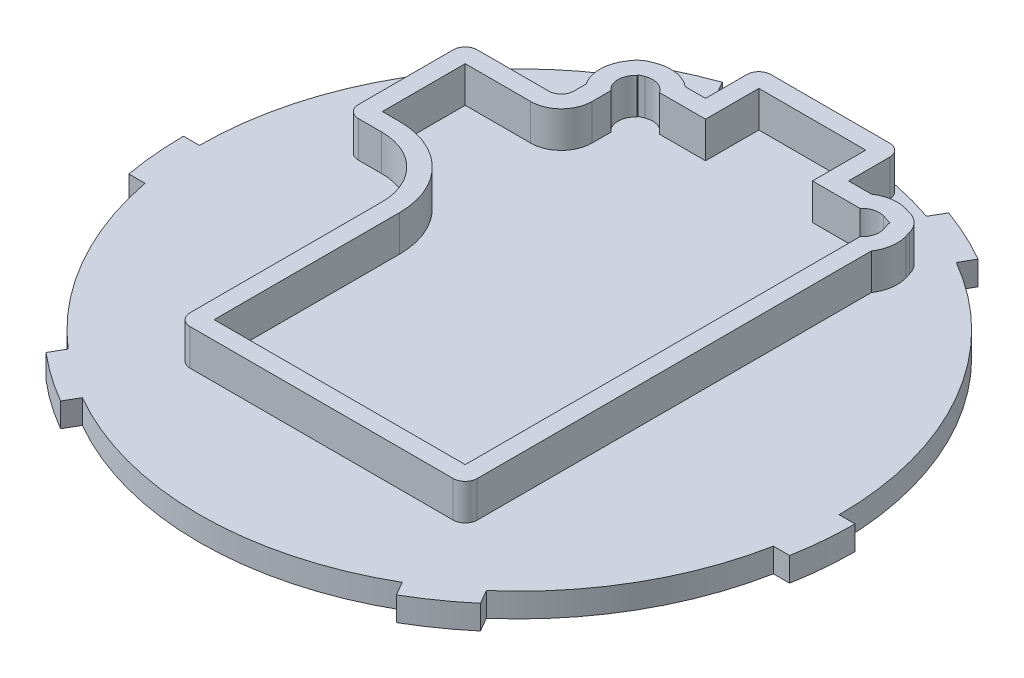
SolidWorks part; units mm, degrees
ref_plane "Front Plane" through (0, 0, 0) normal (0, 0, 1) x (1, 0, 0)
ref_plane "Top Plane" through (0, 0, 0) normal (0, 1, 0) x (1, 0, 0)
ref_plane "Right Plane" through (0, 0, 0) normal (1, 0, 0) x (0, 0, -1)
sketch "Sketch1" plane through (0, 0, 0) normal (0, 1, 0) x (1, 0, 0)
  line L0 (13.3111, 23.0555) -> (13.9742, 24.204) construction
  line L1 (-13.9742, -24.204) -> (-13.3111, -23.0555) construction
  line L2 (-17.4043, -20.1452) -> (-18.0789, -21.3135) construction
  line L3 (13.9742, -24.204) -> (13.3111, -23.0555) construction
  line L4 (17.4043, -20.1452) -> (18.0789, -21.3135) construction
  line L5 (27.4975, -5) -> (26.1484, -5) construction
  line L6 (27.9484, 0) -> (26.6221, 0) construction
  line L7 (9.4186, 26.3135) -> (8.7441, 25.1452) construction
  line L8 (6, 25.9372) -> (6, 21.5) construction
  line L9 (6, 21.5) -> (7.8417, 21.5) construction
  line L10 (12, 17.3417) -> (12, -16.5) construction
  line L11 (12, 17.3417) -> (12, -16.5)
  line L12 (6, 21.5) -> (7.8417, 21.5)
  line L13 (6, 25.9372) -> (6, 21.5)
  line L14 (9.4186, 26.3135) -> (8.7441, 25.1452)
  line L15 (13.3111, 23.0555) -> (13.9742, 24.204)
  line L16 (27.9484, 0) -> (26.6221, 0)
  line L17 (27.4975, -5) -> (26.1484, -5)
  line L18 (17.4043, -20.1452) -> (18.0789, -21.3135)
  line L19 (13.9742, -24.204) -> (13.3111, -23.0555)
  line L20 (-17.4043, -20.1452) -> (-18.0789, -21.3135)
  line L21 (-13.9742, -24.204) -> (-13.3111, -23.0555)
  line L22 (12, -16.5) -> (-12, -16.5) construction
  line L23 (12, -16.5) -> (-12, -16.5)
  line L24 (0, 0) -> (0, -16.5) construction
  line L25 (-13.3111, 23.0555) -> (-13.9742, 24.204) construction
  line L26 (-9.4186, 26.3135) -> (-8.7441, 25.1452) construction
  line L27 (-6, 25.9372) -> (-6, 21.5) construction
  line L28 (-7.6227, 21.5) -> (-6, 21.5) construction
  line L29 (-12, 20.8183) -> (-12, 21.5) construction
  line L30 (-12, 16.5) -> (-12, 17.5017) construction
  line L31 (-20, 15.5) -> (-13, 15.5) construction
  line L32 (-12, -16.5) -> (-12, 0.5) construction
  line L33 (-17, 5.5) -> (-20, 5.5) construction
  line L34 (-20, 5.5) -> (-20, 15.5) construction
  line L35 (-13.3111, 23.0555) -> (-13.9742, 24.204)
  line L36 (-9.4186, 26.3135) -> (-8.7441, 25.1452)
  line L37 (-6, 25.9372) -> (-6, 21.5)
  line L38 (-7.6227, 21.5) -> (-6, 21.5)
  line L39 (-12, 20.8183) -> (-12, 21.5)
  line L40 (-12, 16.5) -> (-12, 17.5017)
  line L41 (-20, 15.5) -> (-13, 15.5)
  line L42 (-12, -16.5) -> (-12, 0.5)
  line L43 (-17, 5.5) -> (-20, 5.5)
  line L44 (-20, 5.5) -> (-20, 15.5)
  line L45 (-26.1484, -5) -> (-27.4975, -5) construction
  line L46 (-26.6221, 0) -> (-27.9484, 0) construction
  line L47 (-26.6221, 0) -> (-27.9484, 0)
  line L48 (-26.1484, -5) -> (-27.4975, -5)
  arc A1 (-13.3111, -23.0555) -> (13.3111, -23.0555) centre (0, 0) ccw construction
  arc A2 (-18.0789, -21.3135) -> (-13.9742, -24.204) centre (0, 0) ccw construction
  arc A3 (-26.1484, -5) -> (-17.4043, -20.1452) centre (0, 0) ccw construction
  arc A4 (13.9742, -24.204) -> (18.0789, -21.3135) centre (0, 0) ccw construction
  arc A5 (17.4043, -20.1452) -> (26.1484, -5) centre (0, 0) ccw construction
  arc A6 (27.4975, -5) -> (27.9484, 0) centre (0, 0) ccw construction
  arc A7 (26.6221, 0) -> (13.3111, 23.0555) centre (0, 0) ccw construction
  arc A8 (13.9742, 24.204) -> (9.4186, 26.3135) centre (0, 0) ccw construction
  arc A9 (8.7441, 25.1452) -> (6, 25.9372) centre (0, 0) ccw construction
  arc A10 (12, 17.3417) -> (12.3619, 19.8996) centre (9.5, 19) ccw construction
  arc A11 (10.3996, 21.8619) -> (7.8417, 21.5) centre (9.5, 19) ccw construction
  arc A12 (10.3996, 21.8619) -> (12, 21.5) centre (13.3982, 31.4018) ccw construction
  arc A13 (12, 21.5) -> (12.3619, 19.8996) centre (21.9018, 22.8982) ccw construction
  arc A14 (12, 17.3417) -> (12.3619, 19.8996) centre (9.5, 19) ccw
  arc A15 (12, 21.5) -> (12.3619, 19.8996) centre (21.9018, 22.8982) ccw
  arc A16 (10.3996, 21.8619) -> (12, 21.5) centre (13.3982, 31.4018) ccw
  arc A17 (10.3996, 21.8619) -> (7.8417, 21.5) centre (9.5, 19) ccw
  arc A18 (8.7441, 25.1452) -> (6, 25.9372) centre (0, 0) ccw
  arc A19 (13.9742, 24.204) -> (9.4186, 26.3135) centre (0, 0) ccw
  arc A20 (26.6221, 0) -> (13.3111, 23.0555) centre (0, 0) ccw
  arc A21 (27.4975, -5) -> (27.9484, 0) centre (0, 0) ccw
  arc A22 (17.4043, -20.1452) -> (26.1484, -5) centre (0, 0) ccw
  arc A23 (13.9742, -24.204) -> (18.0789, -21.3135) centre (0, 0) ccw
  arc A24 (-26.1484, -5) -> (-17.4043, -20.1452) centre (0, 0) ccw
  arc A25 (-18.0789, -21.3135) -> (-13.9742, -24.204) centre (0, 0) ccw
  arc A26 (-13.3111, -23.0555) -> (13.3111, -23.0555) centre (0, 0) ccw
  arc A27 (-13.3111, 23.0555) -> (-26.6221, 0) centre (0, 0) ccw construction
  arc A28 (-9.4186, 26.3135) -> (-13.9742, 24.204) centre (0, 0) ccw construction
  arc A29 (-6, 25.9372) -> (-8.7441, 25.1452) centre (0, 0) ccw construction
  arc A30 (-7.6227, 21.5) -> (-10.6213, 21.9425) centre (-9.5, 19.16) ccw construction
  arc A31 (-12, 21.5) -> (-10.6213, 21.9425) centre (-14.3589, 31.2178) ccw construction
  arc A32 (-12, 20.8183) -> (-12, 17.5017) centre (-9.5, 19.16) ccw construction
  arc A33 (-13, 15.5) -> (-12, 16.5) centre (-13, 16.5) ccw construction
  arc A34 (-12, 0.5) -> (-17, 5.5) centre (-17, 0.5) ccw construction
  arc A35 (-13.3111, 23.0555) -> (-26.6221, 0) centre (0, 0) ccw
  arc A36 (-9.4186, 26.3135) -> (-13.9742, 24.204) centre (0, 0) ccw
  arc A37 (-6, 25.9372) -> (-8.7441, 25.1452) centre (0, 0) ccw
  arc A38 (-7.6227, 21.5) -> (-10.6213, 21.9425) centre (-9.5, 19.16) ccw
  arc A39 (-12, 21.5) -> (-10.6213, 21.9425) centre (-14.3589, 31.2178) ccw
  arc A40 (-12, 20.8183) -> (-12, 17.5017) centre (-9.5, 19.16) ccw
  arc A41 (-13, 15.5) -> (-12, 16.5) centre (-13, 16.5) ccw
  arc A42 (-12, 0.5) -> (-17, 5.5) centre (-17, 0.5) ccw
  arc A43 (-27.9484, 0) -> (-27.4975, -5) centre (0, 0) ccw construction
  arc A44 (-27.9484, 0) -> (-27.4975, -5) centre (0, 0) ccw
  circle A45 centre (0, 0) radius 26.6221
extrude "Boss-Extrude1" add sketch "Sketch1" along normal blind 2 contours L13 A45 L37 L38 A38 A39 L39 A40 L40 A41 L41 L44 L43 A42 L42 L23 L11 A14 A15 A16 A17 L12 | A26 A45 A22 A20 A18 L13 L12 A17 A16 A15 A14 L11 L23 L42 A42 L43 L44 L41 A41 L40 A40 L39 A39 A38 L38 L37 A37 A35 A24 | A45 L15 A19 L14 | A45 L36 A36 L35 | A45 L17 A21 L16 | A45 L19 A23 L18 | A45 L20 A25 L21 | A45 L47 A44 L48 region at (13.2112, 0, -18.4749) region at (-1.2783, 0, -4.3933) region at (11.3943, 0, -24.7497) region at (-11.3943, 0, -24.7497) region at (27.131, 0, 2.5071) region at (-27.131, 0, 2.5071) region at (15.7367, 0, 22.2426) region at (-15.7367, 0, 22.2426)
sketch "Sketch2" plane through (0, 0, 0) normal (0, -1, 0) x (1, 0, 0)
  line L0 (-6, -25.9372) -> (6, -25.9372) construction
  line L1 (-5.95, -25.8872) -> (5.95, -25.8872)
  line L2 (5.95, -21.45) -> (5.95, -25.8872)
  line L3 (7.8568, -21.45) -> (5.95, -21.45)
  line L4 (11.95, 16.45) -> (11.95, -17.3568)
  line L5 (-11.95, 16.45) -> (11.95, 16.45)
  line L6 (-11.95, -0.5) -> (-11.95, 16.45)
  line L7 (-19.95, -5.55) -> (-17, -5.55)
  line L8 (-19.95, -15.45) -> (-19.95, -5.55)
  line L9 (-13, -15.45) -> (-19.95, -15.45)
  line L10 (-11.95, -17.5168) -> (-11.95, -16.5)
  line L11 (-11.95, -21.4608) -> (-11.95, -20.8031)
  line L12 (-5.95, -21.45) -> (-7.6404, -21.45)
  line L13 (-5.95, -25.8872) -> (-5.95, -21.45)
  line L24 (-12, -0.5) -> (-12, 16.5)
  line L25 (-12, 16.5) -> (12, 16.5)
  line L26 (12, 16.5) -> (12, -17.3417)
  line L27 (7.8417, -21.5) -> (6, -21.5)
  line L28 (6, -21.5) -> (6, -25.9372)
  line L29 (8.7441, -25.1452) -> (9.4186, -26.3135)
  line L30 (13.9742, -24.204) -> (13.3111, -23.0555)
  line L31 (26.6221, 0) -> (27.9484, 0)
  line L32 (27.4975, 5) -> (26.1484, 5)
  line L33 (17.4043, 20.1452) -> (18.0789, 21.3135)
  line L34 (13.9742, 24.204) -> (13.3111, 23.0555)
  line L35 (-13.3111, 23.0555) -> (-13.9742, 24.204)
  line L36 (-18.0789, 21.3135) -> (-17.4043, 20.1452)
  line L37 (-26.1484, 5) -> (-27.4975, 5)
  line L38 (-27.9484, 0) -> (-26.6221, 0)
  line L39 (-13.3111, -23.0555) -> (-13.9742, -24.204)
  line L40 (-9.4186, -26.3135) -> (-8.7441, -25.1452)
  line L41 (-6, -25.9372) -> (-6, -21.5)
  line L42 (-6, -21.5) -> (-7.6227, -21.5)
  line L43 (-12, -21.5) -> (-12, -20.8183)
  line L44 (-12, -17.5017) -> (-12, -16.5)
  line L45 (-13, -15.5) -> (-20, -15.5)
  line L46 (-20, -15.5) -> (-20, -5.5)
  line L47 (-20, -5.5) -> (-17, -5.5)
  line L48 (-12, -0.5) -> (-12, 16.5) construction
  line L49 (-12, 16.5) -> (12, 16.5) construction
  line L50 (12, 16.5) -> (12, -17.3417) construction
  line L51 (7.8417, -21.5) -> (6, -21.5) construction
  line L52 (6, -21.5) -> (6, -25.9372) construction
  line L65 (-6, -25.9372) -> (-6, -21.5) construction
  line L66 (-6, -21.5) -> (-7.6227, -21.5) construction
  line L67 (-12, -21.5) -> (-12, -20.8183) construction
  line L68 (-12, -17.5017) -> (-12, -16.5) construction
  line L69 (-13, -15.5) -> (-20, -15.5) construction
  line L70 (-20, -15.5) -> (-20, -5.5) construction
  line L71 (-20, -5.5) -> (-17, -5.5) construction
  arc A0 (7.8568, -21.45) -> (10.3846, -21.8142) centre (9.5, -19) ccw
  arc A1 (11.9558, -21.4558) -> (10.3846, -21.8142) centre (13.3982, -31.4018) ccw
  arc A3 (12.3142, -19.8846) -> (11.9558, -21.4558) centre (21.9018, -22.8982) ccw
  arc A4 (12.3142, -19.8846) -> (11.95, -17.3568) centre (9.5, -19) ccw
  arc A5 (-17, -5.55) -> (-11.95, -0.5) centre (-17, -0.5) ccw
  arc A6 (-11.95, -16.5) -> (-13, -15.45) centre (-13, -16.5) ccw
  arc A7 (-11.95, -17.5168) -> (-11.95, -20.8031) centre (-9.5, -19.16) ccw
  arc A8 (-10.6026, -21.8962) -> (-11.95, -21.4608) centre (-14.3589, -31.2178) ccw
  arc A9 (-10.6026, -21.8962) -> (-7.6404, -21.45) centre (-9.5, -19.16) ccw
  arc A24 (12.3619, -19.8996) -> (12, -17.3417) centre (9.5, -19) ccw
  arc A25 (12.3619, -19.8996) -> (12, -21.5) centre (21.9018, -22.8982) ccw
  arc A26 (12, -21.5) -> (10.3996, -21.8619) centre (13.3982, -31.4018) ccw
  arc A27 (7.8417, -21.5) -> (10.3996, -21.8619) centre (9.5, -19) ccw
  arc A28 (6, -25.9372) -> (8.7441, -25.1452) centre (0, 0) ccw
  arc A29 (9.4186, -26.3135) -> (13.9742, -24.204) centre (0, 0) ccw
  arc A30 (13.3111, -23.0555) -> (26.6221, 0) centre (0, 0) ccw
  arc A31 (27.9484, 0) -> (27.4975, 5) centre (0, 0) ccw
  arc A32 (26.1484, 5) -> (17.4043, 20.1452) centre (0, 0) ccw
  arc A33 (18.0789, 21.3135) -> (13.9742, 24.204) centre (0, 0) ccw
  arc A34 (13.3111, 23.0555) -> (-13.3111, 23.0555) centre (0, 0) ccw
  arc A35 (-13.9742, 24.204) -> (-18.0789, 21.3135) centre (0, 0) ccw
  arc A36 (-17.4043, 20.1452) -> (-26.1484, 5) centre (0, 0) ccw
  arc A37 (-27.4975, 5) -> (-27.9484, 0) centre (0, 0) ccw
  arc A38 (-26.6221, 0) -> (-13.3111, -23.0555) centre (0, 0) ccw
  arc A39 (-13.9742, -24.204) -> (-9.4186, -26.3135) centre (0, 0) ccw
  arc A40 (-8.7441, -25.1452) -> (-6, -25.9372) centre (0, 0) ccw
  arc A41 (-10.6213, -21.9425) -> (-7.6227, -21.5) centre (-9.5, -19.16) ccw
  arc A42 (-10.6213, -21.9425) -> (-12, -21.5) centre (-14.3589, -31.2178) ccw
  arc A43 (-12, -17.5017) -> (-12, -20.8183) centre (-9.5, -19.16) ccw
  arc A44 (-12, -16.5) -> (-13, -15.5) centre (-13, -16.5) ccw
  arc A45 (-17, -5.5) -> (-12, -0.5) centre (-17, -0.5) ccw
  arc A46 (12.3619, -19.8996) -> (12, -17.3417) centre (9.5, -19) ccw construction
  arc A47 (12.3619, -19.8996) -> (12, -21.5) centre (21.9018, -22.8982) ccw construction
  arc A48 (12, -21.5) -> (10.3996, -21.8619) centre (13.3982, -31.4018) ccw construction
  arc A49 (7.8417, -21.5) -> (10.3996, -21.8619) centre (9.5, -19) ccw construction
  arc A63 (-10.6213, -21.9425) -> (-7.6227, -21.5) centre (-9.5, -19.16) ccw construction
  arc A64 (-10.6213, -21.9425) -> (-12, -21.5) centre (-14.3589, -31.2178) ccw construction
  arc A65 (-12, -17.5017) -> (-12, -20.8183) centre (-9.5, -19.16) ccw construction
  arc A66 (-12, -16.5) -> (-13, -15.5) centre (-13, -16.5) ccw construction
  arc A67 (-17, -5.5) -> (-12, -0.5) centre (-17, -0.5) ccw construction
  dimension "D1" = 0.05
  dimension "D2" = 0
extrude "Boss-Extrude2" add sketch "Sketch2" against normal blind 5
sketch "Sketch4" plane through (0, 5, 0) normal (0, 1, 0) x (-1, 0, 0)
  line L26 (4.45, -24.3872) -> (4.45, -19.95)
  line L27 (-4.45, -24.3872) -> (4.45, -24.3872)
  line L28 (-4.45, -19.95) -> (-4.45, -24.3872)
  line L29 (-8.4046, -19.95) -> (-4.45, -19.95)
  line L30 (-10.45, 14.95) -> (-10.45, -17.9046)
  line L31 (10.45, 14.95) -> (-10.45, 14.95)
  line L32 (10.45, -0.5) -> (10.45, 14.95)
  line L33 (18.45, -7.05) -> (17, -7.05)
  line L34 (18.45, -13.95) -> (18.45, -7.05)
  line L35 (13, -13.95) -> (18.45, -13.95)
  line L36 (10.45, -18.0645) -> (10.45, -16.5)
  line L37 (10.45, -20.3494) -> (10.45, -20.2554)
  line L38 (4.45, -19.95) -> (8.2841, -19.95)
  line L39 (4.45, -24.3872) -> (4.45, -19.95)
  line L40 (-4.45, -24.3872) -> (4.45, -24.3872)
  line L41 (-4.45, -19.95) -> (-4.45, -24.3872)
  line L42 (-8.4046, -19.95) -> (-4.45, -19.95)
  line L43 (-10.45, 14.95) -> (-10.45, -17.9046)
  line L44 (10.45, 14.95) -> (-10.45, 14.95)
  line L45 (10.45, -0.5) -> (10.45, 14.95)
  line L46 (18.45, -7.05) -> (17, -7.05)
  line L47 (18.45, -13.95) -> (18.45, -7.05)
  line L48 (13, -13.95) -> (18.45, -13.95)
  line L49 (10.45, -18.0645) -> (10.45, -16.5)
  line L50 (10.45, -20.3494) -> (10.45, -20.2554)
  line L51 (4.45, -19.95) -> (8.2841, -19.95)
  arc A18 (-9.9348, -20.3833) -> (-8.4046, -19.95) centre (-9.5, -19) ccw
  arc A19 (-9.9348, -20.3833) -> (-10.6769, -20.1769) centre (-13.3982, -31.4018) ccw
  arc A20 (-10.6769, -20.1769) -> (-10.8833, -19.4348) centre (-21.9018, -22.8982) ccw
  arc A21 (-10.45, -17.9046) -> (-10.8833, -19.4348) centre (-9.5, -19) ccw
  arc A22 (10.45, -0.5) -> (17, -7.05) centre (17, -0.5) ccw
  arc A23 (13, -13.95) -> (10.45, -16.5) centre (13, -16.5) ccw
  arc A24 (10.45, -20.2554) -> (10.45, -18.0645) centre (9.5, -19.16) ccw
  arc A25 (10.45, -20.3494) -> (10.042, -20.5049) centre (14.3589, -31.2178) ccw
  arc A26 (8.2841, -19.95) -> (10.042, -20.5049) centre (9.5, -19.16) ccw
  arc A27 (-9.9348, -20.3833) -> (-8.4046, -19.95) centre (-9.5, -19) ccw
  arc A28 (-9.9348, -20.3833) -> (-10.6769, -20.1769) centre (-13.3982, -31.4018) ccw
  arc A29 (-10.6769, -20.1769) -> (-10.8833, -19.4348) centre (-21.9018, -22.8982) ccw
  arc A30 (-10.45, -17.9046) -> (-10.8833, -19.4348) centre (-9.5, -19) ccw
  arc A31 (10.45, -0.5) -> (17, -7.05) centre (17, -0.5) ccw
  arc A32 (13, -13.95) -> (10.45, -16.5) centre (13, -16.5) ccw
  arc A33 (10.45, -20.2554) -> (10.45, -18.0645) centre (9.5, -19.16) ccw
  arc A34 (10.45, -20.3494) -> (10.042, -20.5049) centre (14.3589, -31.2178) ccw
  arc A35 (8.2841, -19.95) -> (10.042, -20.5049) centre (9.5, -19.16) ccw
  dimension "D1" = 1.5
extrude "Cut-Extrude1" cut sketch "Sketch4" against normal blind 3
fillet "Fillet1" radius 2 2 edges at (11.9558, 3.5, -21.4558) (-11.95, 3.5, -21.4608)
fillet "Fillet2" radius 1 6 edges at (11.95, 3.5, 16.45) (-11.95, 3.5, 16.45) (-19.95, 3.5, -5.55) (-19.95, 3.5, -15.45) (5.95, 3.5, -25.8872) (-5.95, 3.5, -25.8872)
